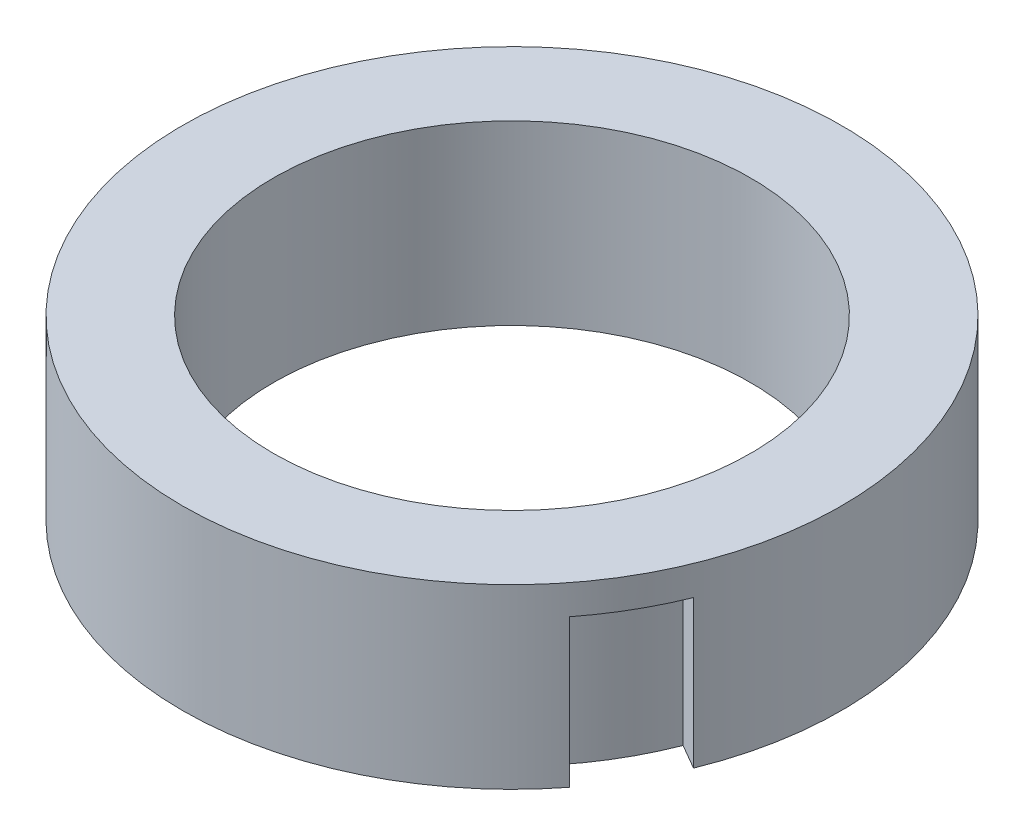
SolidWorks part; units mm, degrees
ref_plane "Front Plane" through (0, 0, 0) normal (0, 0, 1) x (1, 0, 0)
ref_plane "Top Plane" through (0, 0, 0) normal (0, 1, 0) x (1, 0, 0)
ref_plane "Right Plane" through (0, 0, 0) normal (1, 0, 0) x (0, 0, -1)
sketch "Sketch1" plane through (0, 0, 0) normal (0, 1, 0) x (1, 0, 0)
  line L0 (0, 0) -> (0, 14.5) construction
  line L1 (-2, 13.0982) -> (-2, 14.3614)
  line L2 (2, 13.0982) -> (2, 14.3614)
  line L3 (-2, 13.7298) -> (2, 13.7298) construction
  line L4 (12.3434, -4.817) -> (13.4373, -5.4487)
  line L5 (10.3434, -8.2811) -> (11.4373, -8.9128)
  line L6 (-10.3434, -8.2811) -> (-11.4373, -8.9128)
  line L7 (-12.3434, -4.817) -> (-13.4373, -5.4487)
  circle A0 centre (0, 0) radius 14.5
  circle A1 centre (0, 0) radius 10.5
  circle A2 centre (0, 0) radius 13.25
  point P12 (0, 13.7298)
  point P23 (0, 0)
  dimension "D1" = 29
  dimension "D2" = 21
  dimension "D3" = 26.5
  dimension "D4" = 4
  dimension "D5" = 3
extrude "Boss-Extrude1" add sketch "Sketch1" against normal blind 6.5 contours A2 A1 | A2 L6 A0 L5 | A2 L4 A0 L2 | A2 L1 A0 L7 region at (-11.6777, 0, -6.7421) region at (0, 0, -12.8752) region at (2.2342, 0, -13.7298) region at (0, 0, 13.487)
extrude "Boss-Extrude2" add sketch "Sketch1<3>" along normal blind 1.3 contours A2 L1 A0 L7 | A2 A1 | A2 L5 A0 L4 | A2 L6 A0 L5 | A2 L7 A0 L6 | A2 L4 A0 L2 | A2 L2 A0 L1 region at (-11.6777, 0, -6.7421) region at (0, 0, -13.8266) region at (0, 0, -12.8752) region at (2.2342, 0, -13.7298) region at (-11.9742, 0, 6.9133) region at (0, 0, 13.487) region at (11.9742, 0, 6.9133)
sketch "Sketch1<3>" plane through (0, 0, 0) normal (0, 1, 0) x (1, 0, 0) same geometry as "Sketch1"
